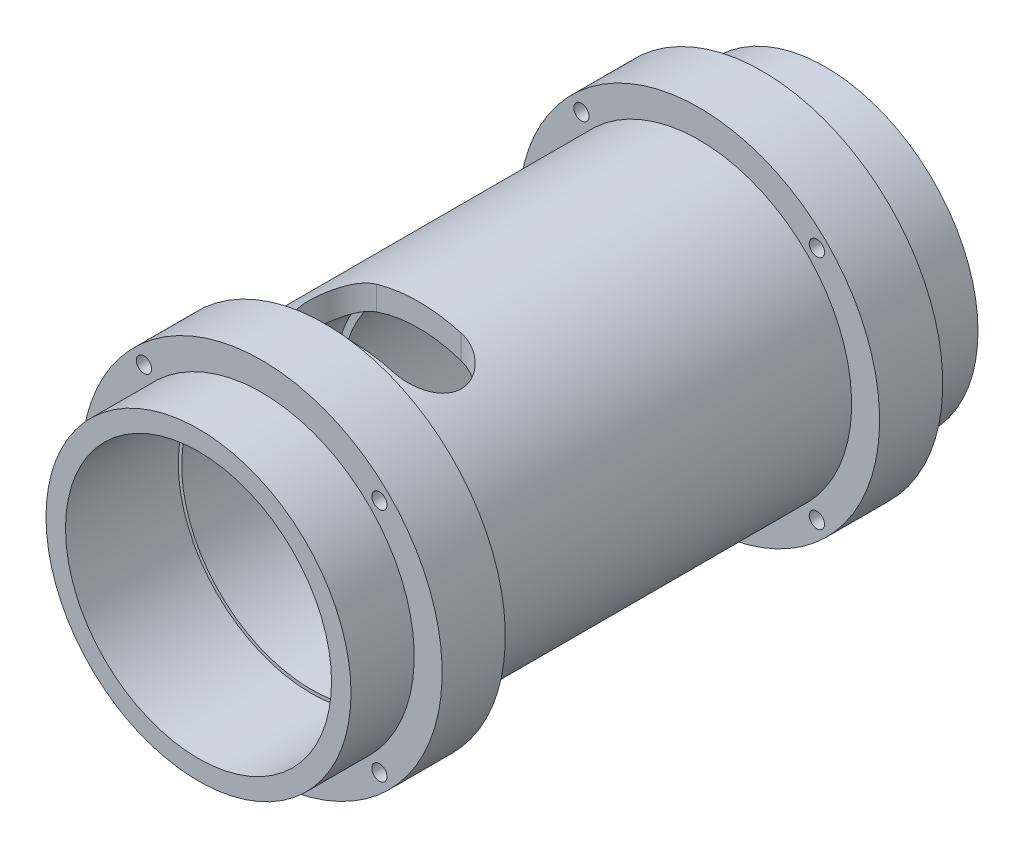
SolidWorks part; units mm, degrees
ref_plane "Front Plane" through (0, 0, 0) normal (0, 0, 1) x (1, 0, 0)
ref_plane "Top Plane" through (0, 0, 0) normal (0, 1, 0) x (1, 0, 0)
ref_plane "Right Plane" through (0, 0, 0) normal (1, 0, 0) x (0, 0, -1)
sketch "Sketch1" plane through (0, 0, 0) normal (0, 0, 1) x (1, 0, 0)
  circle A0 centre (0, 0) radius 33.75
  circle A1 centre (0, 0) radius 45
  dimension "D1" = 67.5
  dimension "D2" = 90
extrude "Boss-Extrude1" add sketch "Sketch1" along normal mid plane 185
sketch "Sketch2" plane through (0, 0, 0) normal (0, 1, 0) x (1, 0, 0)
  line L0 (0, -92.5) -> (0, 92.5)
  line L1 (-45, -92.5) -> (45, -92.5) construction
  line L2 (33.75, 92.5) -> (-33.75, 92.5) construction
  line L3 (0, -92.5) -> (-39.25, -92.5)
  line L4 (-39.25, -92.5) -> (-39.25, -59.2129)
  line L5 (-39.25, -59.2129) -> (-38.25, -59.2129)
  line L6 (-38.25, -59.2129) -> (-38.25, -13.85)
  line L7 (-38.25, -13.85) -> (-36.25, -13.85)
  line L8 (-36.25, -13.85) -> (-36.25, 86.15)
  line L9 (-36.25, 86.15) -> (-38.25, 86.15)
  line L10 (-38.25, 86.15) -> (-38.25, 92.5)
  line L11 (-38.25, 92.5) -> (0, 92.5)
  dimension "D1" = 39.25
  dimension "D2" = 33.2871
  dimension "D3" = 38.25
  dimension "D4" = 78.65
  dimension "D5" = 178.65
  dimension "D6" = 36.25
revolve "Cut-Revolve1" cut sketch "Sketch2" angle 360 about L0
sketch "Sketch3" plane through (0, 0, 0) normal (0, 1, 0) x (1, 0, 0)
  line L0 (-12.5, -37.5) -> (12.5, -37.5) construction
  line L1 (-12.5, -27.5) -> (12.5, -27.5)
  line L2 (-12.5, -47.5) -> (12.5, -47.5)
  line L3 (-45, -92.5) -> (45, -92.5) construction
  arc A0 (-12.5, -27.5) -> (-12.5, -47.5) centre (-12.5, -37.5) ccw
  arc A1 (12.5, -47.5) -> (12.5, -27.5) centre (12.5, -37.5) ccw
  point P2 (0, -37.5)
  dimension "D3" = 10
  dimension "D1" = 55
  dimension "D2" = 25
extrude "Cut-Extrude1" cut sketch "Sketch3" along normal through all
sketch "Sketch4" plane through (0, 0, 0) normal (1, 0, 0) x (0, 0, -1)
  line L0 (-73.8582, 45) -> (-73.8582, 53.25)
  line L1 (-47.5, 45) -> (-92.5, 45) construction
  line L2 (-73.8582, 53.25) -> (-55.2164, 53.25)
  line L3 (-55.2164, 53.25) -> (-55.2164, 45)
  line L4 (-55.2164, 45) -> (-73.8582, 45)
  line L5 (-92.5, 45) -> (-92.5, -45) construction
  line L6 (-73.8582, 45) -> (-92.5, 45) construction
  line L7 (0, 0) -> (0, 45) construction
  line L8 (92.5, 45) -> (-27.5, 45) construction
  line L9 (55.2164, 53.25) -> (55.2164, 45)
  line L10 (73.8582, 53.25) -> (55.2164, 53.25)
  line L11 (73.8582, 45) -> (73.8582, 53.25)
  line L12 (55.2164, 45) -> (73.8582, 45)
  line L13 (92.5, 0) -> (-92.5, 0) construction
  line L14 (92.5, -45) -> (92.5, 45) construction
  dimension "D1" = 18.6418
  dimension "D2" = 8.25
revolve "Revolve1" add sketch "Sketch4" angle 360 about L13
sketch "Sketch7" plane through (0, 0, 73.8582) normal (0, 0, 1) x (1, 0, 0)
  line L0 (0, 45) -> (0, 53.25) construction
  line L1 (0, 0) -> (49.125, 0) construction
  line L2 (0, 0) -> (-34.7366, 34.7366) construction
  circle A0 centre (0, 0) radius 45 construction
  circle A1 centre (0, 0) radius 53.25 construction
  circle A2 centre (0, 0) radius 49.125 construction
  point P10 (0, 49.125)
  point P11 (-34.7366, 34.7366)
  point P13 (34.7366, 34.7366)
  point P14 (-34.7366, -34.7366)
  point P16 (34.7366, -34.7366)
  dimension "D1" = 45
hole_wizard "M4 Clearance Hole1" positions "Sketch7" profile "Sketch8" hole size "M4" standard "ANSI Metric" end condition through all
sketch "Sketch8" plane through (34.7366, -34.7366, 73.8582) normal (1, 0, 0) x (0, -1, 0)
  line L0 (0, 0) -> (0, 166.3582)
  line L1 (0, 166.3582) -> (2.25, 166.3582)
  line L2 (2.25, 166.3582) -> (2.25, 0)
  line L5 (2.25, 0) -> (0, 0)
  line L11 (0, -6.35) -> (0, 107.95) construction
  dimension "Thru Hole Dia." = 4.5
  dimension "Thru Hole Depth" = 166.3582
